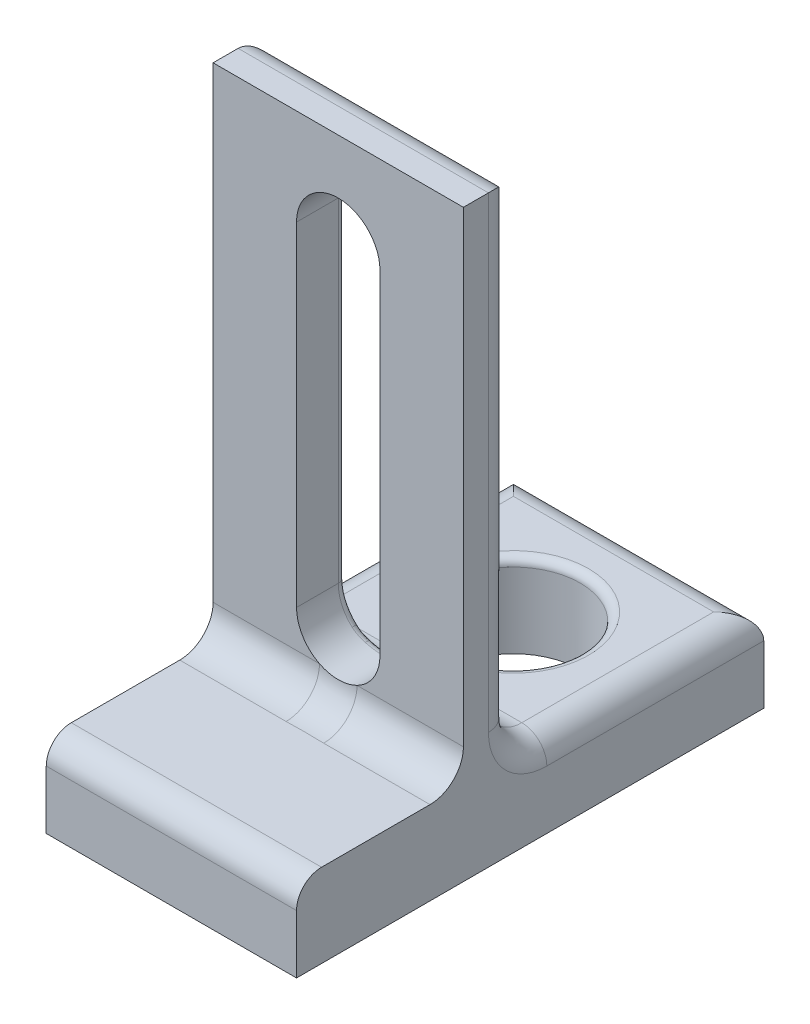
SolidWorks part; units mm, degrees
ref_plane "Piano frontale" through (0, 0, 0) normal (0, 0, 1) x (1, 0, 0)
ref_plane "Piano superiore" through (0, 0, 0) normal (0, 1, 0) x (1, 0, 0)
ref_plane "Piano destro" through (0, 0, 0) normal (1, 0, 0) x (0, 0, -1)
sketch "Schizzo1" plane through (0, 0, 0) normal (1, 0, 0) x (0, 0, -1)
  line L0 (0, 5) -> (0, 35)
  line L1 (0, 35) -> (3, 35)
  line L2 (3, 35) -> (3, 5)
  line L3 (3, 5) -> (18, 5)
  line L4 (18, 5) -> (18, 0)
  line L5 (18, 0) -> (0, 0)
  line L6 (0, 5) -> (-10, 5)
  line L7 (-10, 5) -> (-10, 0)
  line L8 (-10, 0) -> (0, 0)
  dimension "D1" = 5
  dimension "D2" = 18
  dimension "D3" = 35
  dimension "D4" = 3
  dimension "D5" = 15
  dimension "D6" = 10
extrude "Estrusione-Estrusione1" add sketch "Schizzo1" along normal blind 15
sketch "Schizzo2" plane through (0, 5, 0) normal (0, 1, 0) x (1, 0, 0)
  line L0 (7.5, 18) -> (7.5, 10.5) construction
  line L1 (15, 18) -> (0, 18) construction
  circle A0 centre (7.5, 10.5) radius 4
  dimension "D1" = 8
extrude "Taglio-Estrusione1" cut sketch "Schizzo2" against normal blind 15
sketch "Schizzo3" plane through (0, 0, -3) normal (0, 0, -1) x (-1, 0, 0)
  line L0 (-7.5, 35) -> (-7.5, 19.232) construction
  line L1 (-15, 35) -> (0, 35) construction
  line L2 (-7.5, 9.232) -> (-7.5, 29.232) construction
  line L3 (-10, 9.232) -> (-10, 29.232)
  line L4 (-5, 9.232) -> (-5, 29.232)
  arc A0 (-10, 9.232) -> (-5, 9.232) centre (-7.5, 9.232) ccw
  arc A1 (-5, 29.232) -> (-10, 29.232) centre (-7.5, 29.232) ccw
  point P5 (-7.5, 19.232)
extrude "Taglio-Estrusione2" cut sketch "Schizzo3" against normal blind 15
fillet "Raccordo1" radius 2 2 edges at (7.5, 5, -3) (7.5, 5, 0)
fillet "Raccordo2" radius 1.5 9 edges at (7.5, 5, -18) (7.5, 5, 10) (15, 5, -11.5) (15, 5.5858, -3.5858) (0, 5, -11.5) (0, 5.5858, -3.5858) (7.5, 35, -3) (15, 21, -3) (0, 21, -3)
fillet "Raccordo3" radius 0.5 7 edges at (7.5, 31.732, -3) (5, 19.232, -3) (5.371, 7.9215, -3) (7.5, 6.732, -3) (9.629, 7.9215, -3) (10, 19.232, -3) (7.5, 5, -6.5)
